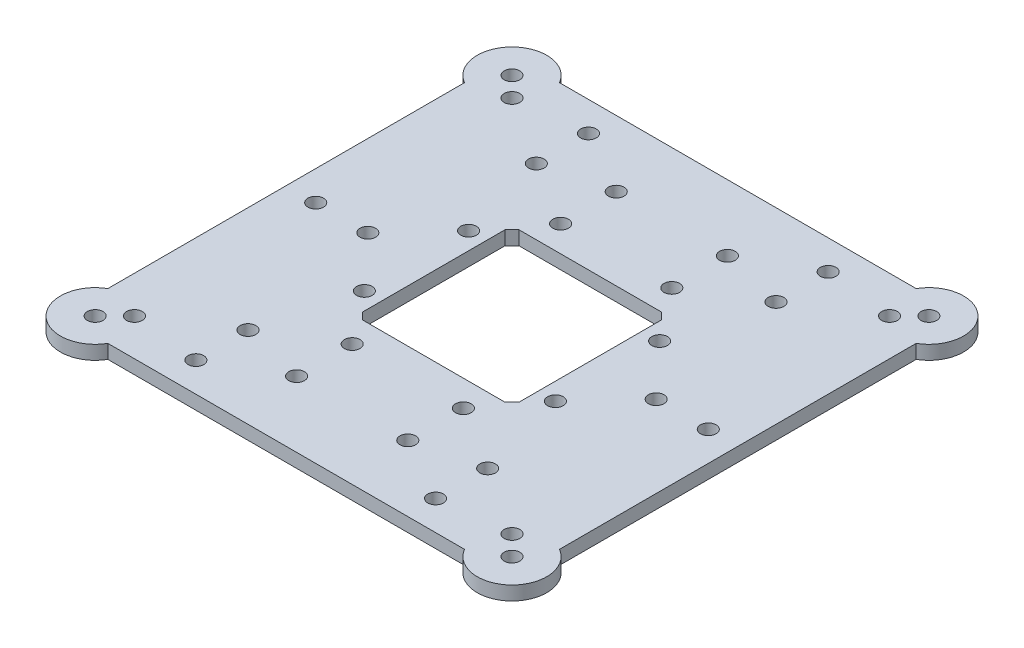
SolidWorks part; units mm, degrees
material "1060 Alloy"
ref_plane "Front Plane" through (0, 0, 0) normal (0, 0, 1) x (1, 0, 0)
ref_plane "Top Plane" through (0, 0, 0) normal (0, 1, 0) x (1, 0, 0)
ref_plane "Right Plane" through (0, 0, 0) normal (1, 0, 0) x (0, 0, -1)
sketch "Sketch1" plane through (0, 0, 0) normal (0, 1, 0) x (1, 0, 0)
  line L0 (60, -60) -> (-60, 60) construction
  line L1 (-60, 60) -> (60, 60) construction
  line L2 (-60, 60) -> (-60, -60) construction
  line L3 (-60, -60) -> (60, -60) construction
  line L4 (60, 60) -> (60, -60) construction
  line L5 (-60, 0) -> (-60, 42.6795)
  line L6 (-42.6795, 60) -> (0, 60)
  line L7 (60, 42.6795) -> (60, 0)
  line L8 (0, 60) -> (42.6795, 60)
  line L9 (42.6795, -60) -> (0, -60)
  line L10 (60, 0) -> (60, -42.6795)
  line L11 (-60, -42.6795) -> (-60, 0)
  line L12 (0, -60) -> (-42.6795, -60)
  line L13 (-60, 0) -> (60, 0) construction
  line L14 (0, 60) -> (0, -60) construction
  circle A0 centre (-60, 60) radius 2.25
  circle A1 centre (60, 60) radius 2.25
  circle A2 centre (60, -60) radius 2.25
  circle A3 centre (-60, -60) radius 2.25
  arc A4 (-65, 51.3397) -> (-51.3397, 65) centre (-60, 60) cw
  arc A5 (51.3397, 65) -> (65, 51.3397) centre (60, 60) cw
  arc A6 (65, -51.3397) -> (51.3397, -65) centre (60, -60) cw
  arc A7 (-51.3397, -65) -> (-65, -51.3397) centre (-60, -60) cw
  arc A8 (-60, -42.6795) -> (-65, -51.3397) centre (-70, -42.6795) cw
  arc A9 (-51.3397, -65) -> (-42.6795, -60) centre (-42.6795, -70) cw
  arc A10 (65, -51.3397) -> (60, -42.6795) centre (70, -42.6795) cw
  arc A11 (60, 42.6795) -> (65, 51.3397) centre (70, 42.6795) cw
  arc A12 (51.3397, 65) -> (42.6795, 60) centre (42.6795, 70) cw
  arc A13 (-51.3397, 65) -> (-42.6795, 60) centre (-42.6795, 70) ccw
  arc A14 (-60, 42.6795) -> (-65, 51.3397) centre (-70, 42.6795) ccw
  arc A15 (42.6795, -60) -> (51.3397, -65) centre (42.6795, -70) cw
  point P32 (0, 0)
  point P38 (-50, 60)
  point P41 (-60, 50)
  dimension "D2" = 4.5
  dimension "D3" = 10
  dimension "D5" = 10
  dimension "D6" = 10
  dimension "D1" = 120
  dimension "D4" = 4
sheet metal parameters "Sheet-Metal1" thickness 4 parameters "D1"=5
base flange "Base-Flange1" sketch "Sketch1" thickness 4 reverse thickness direction no parameters "D1"=5
sketch "Sketch4" plane through (0, 0, 0) normal (0, 1, 0) x (1, 0, 0)
  line L0 (60, -60) -> (-60, 60) construction
  line L1 (-20.5, 22.5) -> (20.5, 22.5)
  line L2 (-22.5, 20.5) -> (-22.5, -20.5)
  line L3 (-20.5, -22.5) -> (20.5, -22.5)
  line L4 (22.5, 20.5) -> (22.5, -20.5)
  line L5 (22.5, 22.5) -> (-22.5, -22.5) construction
  line L6 (-22.5, 20.5) -> (-20.5, 22.5)
  line L7 (-22.5, -20.5) -> (-20.5, -22.5)
  line L8 (20.5, -22.5) -> (22.5, -20.5)
  line L9 (20.5, 22.5) -> (22.5, 20.5)
  point P0 (-22.5, 22.5)
  point P1 (22.5, -22.5)
  dimension "D1" = 45
extrude "Cut-Extrude1" cut sketch "Sketch4" against normal up to next normal cut yes
sketch "Sketch5" plane through (0, -4, 0) normal (0, -1, 0) x (1, 0, 0)
  line L0 (-60, 60) -> (-54.3431, 54.3431) construction
  line L1 (-54.3431, 54.3431) -> (0, 0) construction
  line L2 (60, 60) -> (54.3431, 54.3431) construction
  line L3 (54.3431, 54.3431) -> (0, 0) construction
  line L4 (60, -60) -> (54.3431, -54.3431) construction
  line L5 (54.3431, -54.3431) -> (0, 0) construction
  line L6 (-60, -60) -> (-54.3431, -54.3431) construction
  line L7 (-54.3431, -54.3431) -> (0, 0) construction
  circle A0 centre (-54.3431, 54.3431) radius 2.25
  circle A1 centre (54.3431, 54.3431) radius 2.25
  circle A2 centre (54.3431, -54.3431) radius 2.25
  circle A3 centre (-54.3431, -54.3431) radius 2.25
  point P18 (0, 0)
  dimension "D1" = 4.5
  dimension "D2" = 8
  dimension "D3" = 4
extrude "Cut-Extrude2" cut sketch "Sketch5" against normal through all normal cut yes
sketch "Sketch6" plane through (0, -4, 0) normal (0, -1, 0) x (1, 0, 0)
  line L0 (-27.5, 15) -> (27.5, 15) construction
  line L1 (27.5, 15) -> (27.5, -15) construction
  line L2 (27.5, -15) -> (-27.5, -15) construction
  line L3 (-27.5, -15) -> (-27.5, 15) construction
  line L4 (-27.5, 15) -> (27.5, -15) construction
  circle A0 centre (27.5, 15) radius 2.25
  circle A1 centre (27.5, -15) radius 2.25
  circle A2 centre (-27.5, -15) radius 2.25
  circle A3 centre (-27.5, 15) radius 2.25
  dimension "D3" = 4.5
  dimension "D1" = 55
  dimension "D2" = 30
extrude "Cut-Extrude3" cut sketch "Sketch6" against normal through all normal cut yes
sketch "Sketch8" plane through (0, -4, 0) normal (0, -1, 0) x (1, 0, 0)
  line L0 (42.6795, -60) -> (-42.6795, -60) construction
  line L1 (-65, 51.3397) -> (-60, 51.3397)
  line L2 (-65, 51.3397) -> (-65, -51.3397)
  line L3 (-65, -51.3397) -> (-60, -51.3397)
  line L4 (-60, 51.3397) -> (-60, -51.3397)
  line L5 (-51.3397, -65) -> (51.3397, -65)
  line L6 (-51.3397, -65) -> (-51.3397, -60)
  line L7 (-51.3397, -60) -> (51.3397, -60)
  line L8 (51.3397, -65) -> (51.3397, -60)
  line L9 (65, 51.3397) -> (60, 51.3397)
  line L10 (65, 51.3397) -> (65, -51.3397)
  line L11 (65, -51.3397) -> (60, -51.3397)
  line L12 (60, 51.3397) -> (60, -51.3397)
  line L13 (-51.3397, 65) -> (51.3397, 65)
  line L14 (-51.3397, 65) -> (-51.3397, 60)
  line L15 (-51.3397, 60) -> (51.3397, 60)
  line L16 (51.3397, 65) -> (51.3397, 60)
  arc A0 (42.6795, 60) -> (51.3397, 65) centre (42.6795, 70) ccw construction
base flange "Tab1" sketch "Sketch8" thickness 4 reverse thickness direction no parameters "D1"=5
sketch "Sketch7" plane through (0, -4, 0) normal (0, -1, 0) x (1, 0, 0)
  line L0 (-16, 30) -> (-16, 46) construction
  line L1 (0, -60) -> (0, 60) construction
  line L3 (0, 0) -> (17.5, 0) construction
  line L4 (-16, -30) -> (-16, -46) construction
  circle A0 centre (-16, 46) radius 2.25
  circle A1 centre (-16, 30) radius 2.25
  circle A2 centre (16, 30) radius 2.25
  circle A3 centre (16, 46) radius 2.25
  circle A4 centre (16, -46) radius 2.25
  circle A5 centre (16, -30) radius 2.25
  circle A6 centre (-16, -30) radius 2.25
  circle A7 centre (-16, -46) radius 2.25
  dimension "D2" = 4.5
  dimension "D1" = 16
  dimension "D3" = 30
  dimension "D4" = 16
extrude "Cut-Extrude4" cut sketch "Sketch7" against normal through all normal cut yes
sketch "Sketch9" plane through (0, -4, 0) normal (0, -1, 0) x (1, 0, 0)
  line L0 (-34.5, -56.5) -> (-34.5, -41.5) construction
  line L1 (-34.5, -41.5) -> (-34.5, 41.5) construction
  line L2 (-34.5, 41.5) -> (-34.5, 56.5) construction
  line L3 (-56.5, 0) -> (-41.5, 0) construction
  line L4 (-41.5, 0) -> (-34.5, 0) construction
  line L5 (-34.5, 0) -> (34.5, 0) construction
  line L6 (-22.5, 20.5) -> (-22.5, -20.5) construction
  line L7 (0, 0) -> (0, 65) construction
  line L8 (51.3397, 65) -> (-51.3397, 65) construction
  line L9 (41.5, 0) -> (34.5, 0) construction
  line L10 (56.5, 0) -> (41.5, 0) construction
  line L11 (34.5, 41.5) -> (34.5, 56.5) construction
  line L12 (34.5, -41.5) -> (34.5, 41.5) construction
  line L13 (34.5, -56.5) -> (34.5, -41.5) construction
  circle A0 centre (-34.5, 56.5) radius 2.25
  circle A1 centre (-34.5, 41.5) radius 2.25
  circle A2 centre (-56.5, 0) radius 2.25
  circle A3 centre (-41.5, 0) radius 2.25
  circle A4 centre (-34.5, -41.5) radius 2.25
  circle A5 centre (-34.5, -56.5) radius 2.25
  circle A6 centre (34.5, -56.5) radius 2.25
  circle A7 centre (34.5, -41.5) radius 2.25
  circle A8 centre (41.5, 0) radius 2.25
  circle A9 centre (56.5, 0) radius 2.25
  circle A10 centre (34.5, 41.5) radius 2.25
  circle A11 centre (34.5, 56.5) radius 2.25
  dimension "D2" = 4.5
  dimension "D1" = 15
  dimension "D3" = 56.5
  dimension "D4" = 56.5
  dimension "D5" = 12
extrude "Cut-Extrude5" cut sketch "Sketch9" against normal through all normal cut yes
flat pattern "Flat-Pattern1" [suppressed]
sketch "Bend-Lines1" plane through (0, 0, 0) normal (0, 1, 0) x (1, 0, 0)
sketch3d "Bounding-Box1" [suppressed]
  line L0 (0, 27.3205, 0) -> (0, -112.6795, 0) construction
  line L1 (140, 27.3205, 0) -> (140, -112.6795, 0) construction
  line L2 (0, 27.3205, 0) -> (140, 27.3205, 0) construction
  line L3 (0, -112.6795, 0) -> (140, -112.6795, 0) construction
